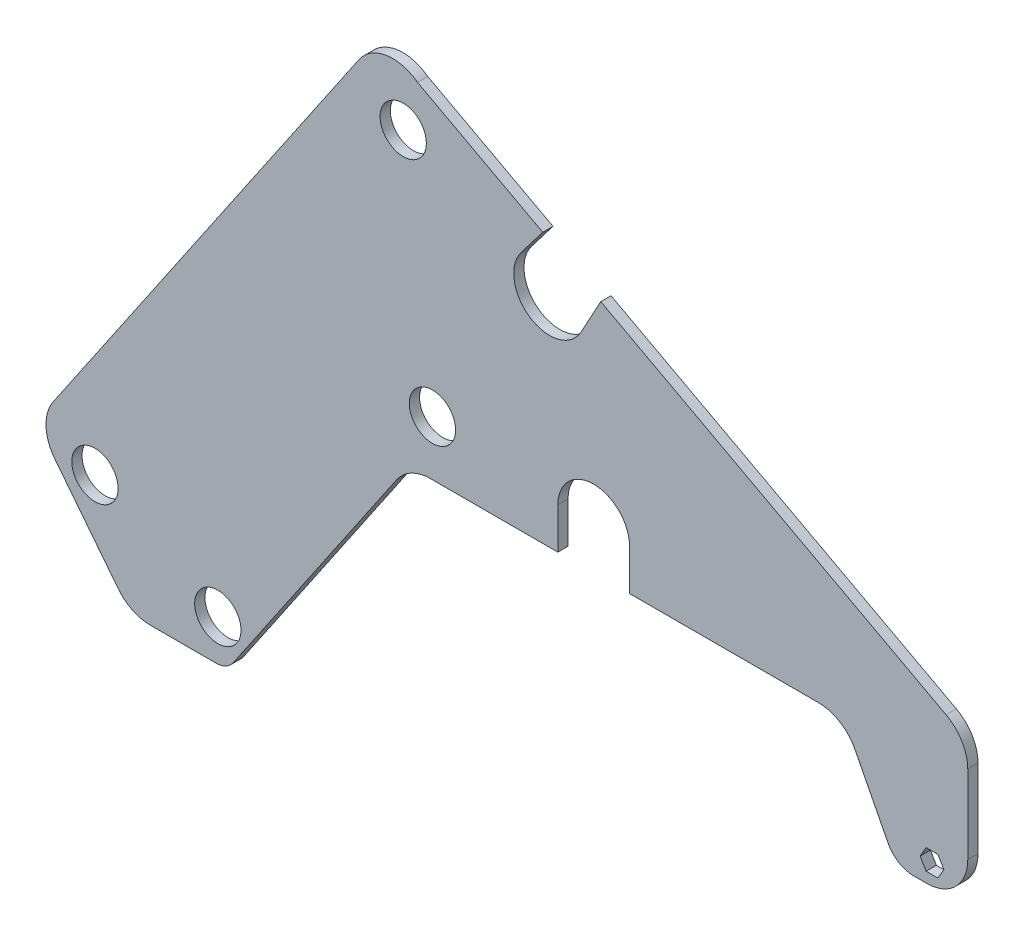
SolidWorks part; units mm, degrees
other "Markup1"
sketch "Sketch1" plane through (-441.7893, 331.8239, 6.35) normal (-0.0431, 0.0102, 0.999) x (0.9985, 0.0354, 0.0427)
sketch "Sketch2" plane through (-413.6701, 343.933, 6.35) normal (-0.0431, 0.0102, 0.999) x (0.9985, 0.0354, 0.0427)
sketch "Sketch3" plane through (-436.3774, 318.5567, 6.35) normal (-0.0431, 0.0102, 0.999) x (0.9985, 0.0354, 0.0427)
sketch "Sketch5" plane through (-436.3774, 318.5567, 6.35) normal (-0.0431, 0.0102, 0.999) x (0.9985, 0.0354, 0.0427)
sketch "Sketch7" plane through (-430.3226, 318.5567, 6.35) normal (-0.0431, 0.0102, 0.999) x (0.9985, 0.0354, 0.0427)
sketch "Sketch9" plane through (-430.3226, 318.5567, 6.35) normal (-0.0431, 0.0102, 0.999) x (0.9985, 0.0354, 0.0427)
other "Markup2"
sketch "Sketch4" plane through (102.4721, 318.5567, 6.35) normal (0.9364, 0.1073, 0.3342) x (0.3416, -0.0598, -0.9379)
sketch "Sketch6" plane through (102.4721, 318.5567, 6.35) normal (0.9364, 0.1073, 0.3342) x (0.3416, -0.0598, -0.9379)
sketch "Sketch8" plane through (141.2086, 318.5567, 6.35) normal (0.9364, 0.1073, 0.3342) x (0.3416, -0.0598, -0.9379)
sketch "Sketch10" plane through (141.2086, 318.5567, 6.35) normal (0.9364, 0.1073, 0.3342) x (0.3416, -0.0598, -0.9379)
material "Lexan"
ref_plane "Front Plane" through (0, 0, 0) normal (0, 0, 1) x (1, 0, 0)
ref_plane "Top Plane" through (0, 0, 0) normal (0, 1, 0) x (1, 0, 0)
ref_plane "Right Plane" through (0, 0, 0) normal (1, 0, 0) x (0, 0, -1)
sketch "Model" plane through (0, 0, 0) normal (0, 0, 1) x (1, 0, 0)
  line L1 (-191.9011, 104.6502) -> (-112.96, 104.6502)
  line L3 (-314.2383, -55.3595) -> (-212.8994, 93.5413)
  line L4 (-236.3032, 307.4477) -> (-425.9209, 28.8361)
  line L5 (-424.8981, -1.1437) -> (-385.5815, -51.2028)
  line L13 (126.3831, 53.8502) -> (122.717, 60.2002)
  line L14 (122.717, 60.2002) -> (115.3846, 60.2002)
  line L15 (115.3846, 60.2002) -> (111.7185, 53.8502)
  line L16 (111.7185, 53.8502) -> (115.3846, 47.5002)
  line L17 (115.3846, 47.5002) -> (122.717, 47.5002)
  line L18 (122.717, 47.5002) -> (126.3831, 53.8502)
  line L19 (-365.606, -60.914) -> (-324.7375, -60.914)
  line L20 (-871.0211, -88.854) -> (370.1019, -88.854) construction
  line L22 (141.2086, 66.5502) -> (141.2086, 78.8846)
  line L27 (107.6196, 41.1502) -> (115.8086, 41.1502)
  line L28 (-399.9752, 2.586) -> (-323.7752, -35.514) construction
  line L29 (-323.7752, -35.514) -> (-190.7071, 138.5169) construction
  line L30 (-190.7071, 138.5169) -> (-208.8329, 283.4378) construction
  line L31 (-208.8329, 283.4378) -> (-399.9752, 2.586) construction
  line L32 (91.8004, 50.8135) -> (71.26, 90.8456)
  line L33 (48.6612, 104.6502) -> (-11.3966, 104.6502)
  line L34 (141.2086, 78.8846) -> (141.2086, 115.3033)
  line L35 (127.8091, 137.6897) -> (-86.3327, 252.4836)
  line L36 (-86.3327, 252.4836) -> (-98.5536, 230.0471)
  line L37 (-112.96, 130.0502) -> (-112.96, 104.6502)
  line L38 (-122.3008, 271.7648) -> (-135.737, 254.1638)
  line L39 (-68.51, 130.0502) -> (-68.51, 104.6502)
  line L40 (-68.51, 104.6502) -> (-2.1388, 104.6502)
  line L41 (-122.3008, 271.7648) -> (-199.9496, 313.3896)
  arc A3 (121.2475, 59.8082) -> (121.352, 60.2002) centre (96.7586, 66.5502) ccw
  circle A9 centre (-323.7752, -35.514) radius 14.351
  circle A10 centre (-399.9752, 2.586) radius 14.351
  circle A12 centre (-190.7071, 138.5169) radius 14.351
  arc A15 (107.6196, 41.1502) -> (91.8004, 50.8135) centre (107.6196, 58.9302) cw
  arc A21 (-191.9011, 104.6502) -> (-212.8994, 93.5413) centre (-191.9011, 79.2502) ccw
  circle A22 centre (-208.8329, 283.4378) radius 14.351
  circle A24 centre (119.0508, 53.8502) radius 6.35 construction
  arc A31 (-324.7375, -60.914) -> (-314.2383, -55.3595) centre (-324.7375, -48.214) ccw
  arc A40 (114.7422, 48.6129) -> (115.0458, 48.9225) centre (96.7586, 66.5502) ccw
  arc A43 (115.8086, 41.1502) -> (141.2086, 66.5502) centre (115.8086, 66.5502) ccw
  arc A44 (-236.3032, 307.4477) -> (-199.9496, 313.3896) centre (-215.305, 293.1567) cw
  arc A45 (-365.606, -60.914) -> (-385.5815, -51.2028) centre (-365.606, -35.514) cw
  arc A46 (71.26, 90.8456) -> (48.6612, 104.6502) centre (48.6612, 79.2502) ccw
  arc A47 (141.2086, 115.3033) -> (127.8091, 137.6897) centre (115.8086, 115.3033) ccw
  arc A48 (-424.8981, -1.1437) -> (-425.9209, 28.8361) centre (-404.9226, 14.5451) cw
  arc A49 (-135.737, 254.1638) -> (-98.5536, 230.0471) centre (-118.0711, 240.678) ccw
  arc A50 (-68.51, 130.0502) -> (-112.96, 130.0502) centre (-90.735, 130.0502) ccw
  ellipse E0 centre (-551.1692, 173.9527) end of major axis (-591.2054, 216.0961) minor radius 17.278
  point P31 (-177.5612, 330.9695)
  point P34 (100.2935, -12.8222)
  point P43 (-377.9543, -60.914)
  point P55 (96.7586, 41.1502)
  point P59 (174.831, 53.8502)
  point P60 (-205.3388, 104.6502)
  point P64 (-436.3774, 13.472)
  dimension "D3" = 38.1
  dimension "D4" = 104.6502
  dimension "D5" = 76.2
  dimension "D6" = 44.45
  dimension "D7" = 12.7
  dimension "D8" = 28.702
  dimension "D11" = 139.7
  dimension "D12" = 27.94
  dimension "D21" = 124.238
  dimension "D13" = 12.7
  dimension "D16" = 355.6
  dimension "D23" = 25.4
  dimension "D24" = 25.4
  dimension "D26" = 25.4
  dimension "D14" = 406.4
  dimension "D20" = 254
  dimension "D29" = 25.4
  dimension "D31" = 25.4
  dimension "D25" = 88.9
  dimension "D30" = 17.78
  dimension "D32" = 25.4
  dimension "D33" = 25.4
  dimension "D34" = 44.45
  dimension "D35" = 25.4
  dimension "D37" = 44.45
  dimension "D38" = 25.4
  dimension "D9" = 19.05
  dimension "D10" = 146.05
  dimension "D15" = 33.8667
  dimension "D17" = 339.725
  dimension "D18" = 219.075
  dimension "D19" = 50.8
  dimension "D22" = 25.4
  dimension "D27" = 53.2168
  dimension "D28" = 12.7
  dimension "D36" = 100.33
  dimension "D39" = 100.33
extrude "Boss-Extrude1" add sketch "Model" along normal blind 6.35 contours L5 L3 L1 L4 A22 A9 A10 A12 region at (-206.9871, 107.7659, 0)
